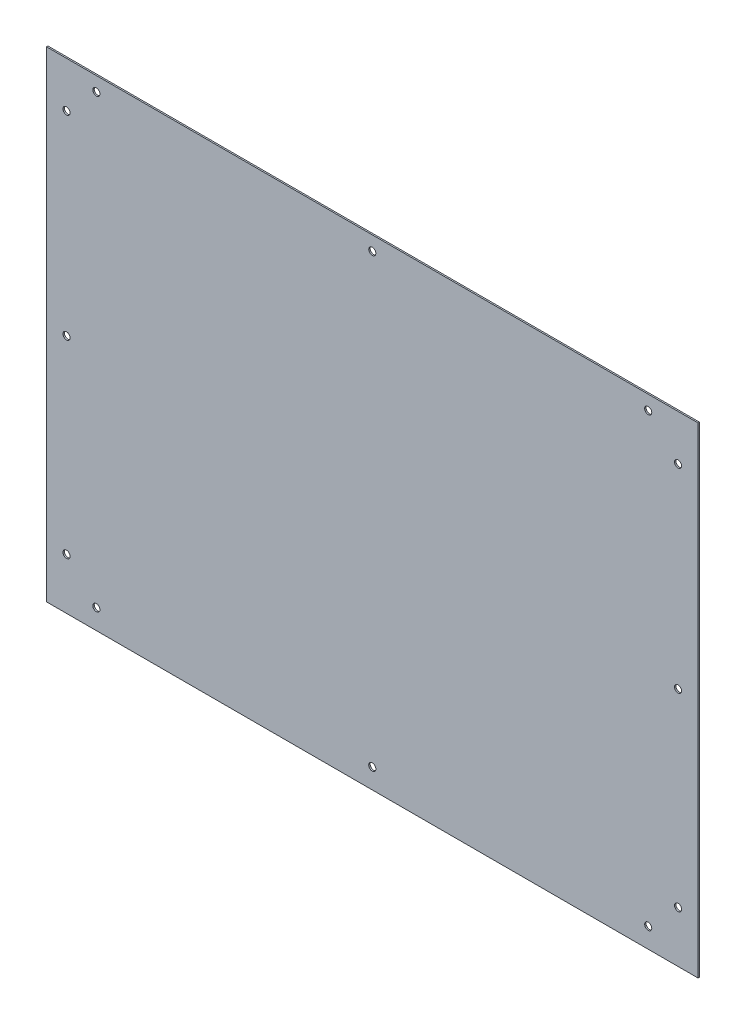
SolidWorks part; units mm, degrees
material "1345 Alloy"
ref_plane "Front Plane" through (0, 0, 0) normal (0, 0, 1) x (1, 0, 0)
ref_plane "Top Plane" through (0, 0, 0) normal (0, 1, 0) x (1, 0, 0)
ref_plane "Right Plane" through (0, 0, 0) normal (1, 0, 0) x (0, 0, -1)
sketch "Sketch1" plane through (0, 0, 0) normal (0, 0, 1) x (1, 0, 0)
  line L1 (-229, 169) -> (229, 169)
  line L2 (-229, 169) -> (-229, -169)
  line L3 (-229, -169) -> (229, -169)
  line L4 (229, 169) -> (229, -169)
  line L5 (-229, 169) -> (229, -169) construction
  line L6 (-229, -169) -> (229, 169) construction
  point P0 (0, 0)
  dimension "D1" = 458
  dimension "D2" = 338
extrude "Boss-Extrude1" add sketch "Sketch1" along normal blind 1
sketch "Sketch2" plane through (0, 0, 1) normal (0, 0, 1) x (1, 0, 0)
  line L6 (-194, -155) -> (-194, -169) construction
  line L8 (194, 159) -> (194, 169) construction
  line L11 (-229, -169) -> (229, -169) construction
  line L12 (229, 0) -> (215, 0) construction
  line L14 (229, 169) -> (-229, 169) construction
  circle A0 centre (-194, 159) radius 2.5
  circle A1 centre (-194, -155) radius 2.5
  circle A2 centre (194, -155) radius 2.5
  circle A3 centre (194, 159) radius 2.5
  circle A4 centre (-215, 0) radius 2.5
  circle A5 centre (-215, -133) radius 2.5
  circle A6 centre (-215, 137) radius 2.5
  circle A7 centre (215, 0) radius 2.5
  circle A8 centre (215, -133) radius 2.5
  circle A9 centre (215, 137) radius 2.5
  circle A10 centre (0, 159) radius 2.5
  circle A11 centre (0, -155) radius 2.5
  dimension "D3" = 5
  dimension "D6" = 5
  dimension "D7" = 5
  dimension "D8" = 5
  dimension "D13" = 5
  dimension "D14" = 5
  dimension "D15" = 5
  dimension "D19" = 5
  dimension "D20" = 5
  dimension "D4" = 215
  dimension "D5" = 215
  dimension "D11" = 36
  dimension "D16" = 14
  dimension "D17" = 14
  dimension "D18" = 14
  dimension "D21" = 194
  dimension "D24" = 194
  dimension "D26" = 32
  dimension "D27" = 137
extrude "Cut-Extrude1" cut sketch "Sketch2" against normal through all
